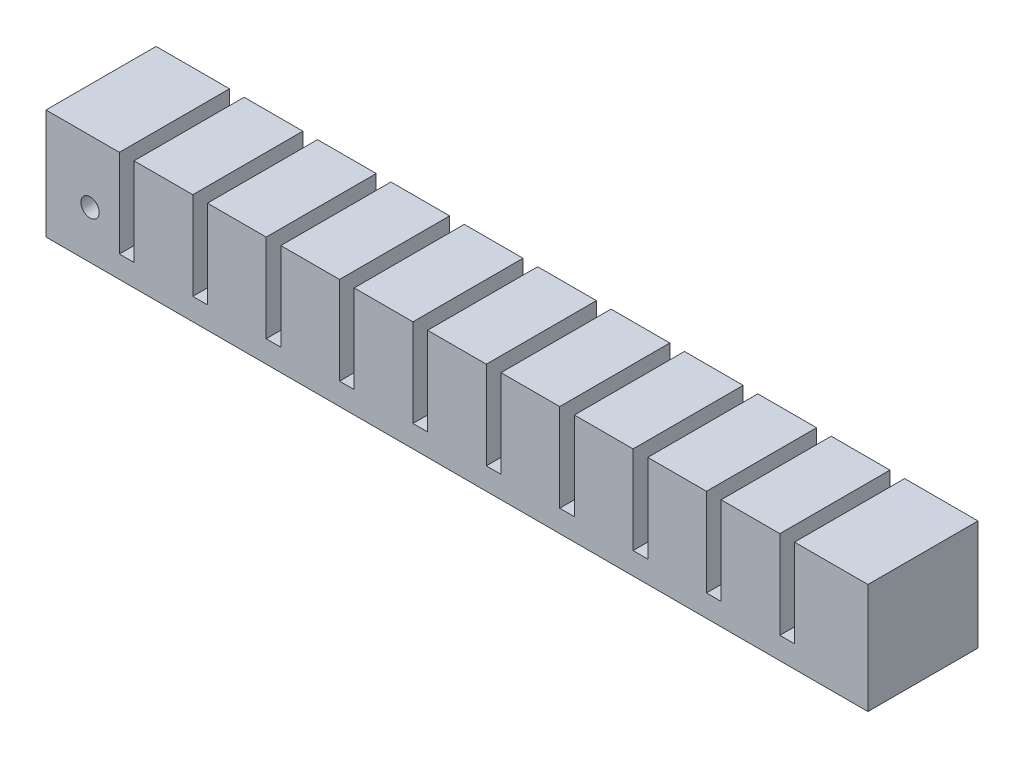
SolidWorks part; units mm, degrees
ref_plane "Front Plane" through (0, 0, 0) normal (0, 0, 1) x (1, 0, 0)
ref_plane "Top Plane" through (0, 0, 0) normal (0, 1, 0) x (1, 0, 0)
ref_plane "Right Plane" through (0, 0, 0) normal (1, 0, 0) x (0, 0, -1)
sketch "Sketch1" plane through (0, 0, 0) normal (0, 0, 1) x (1, 0, 0)
  line L1 (0, 0) -> (8, 0)
  line L2 (0, 0) -> (0, 15)
  line L3 (0, 15) -> (8, 15)
  line L4 (8, 0) -> (8, 15)
  dimension "D1" = 8
  dimension "D2" = 15
extrude "first chamber block" add sketch "Sketch1" along normal blind 15
sketch "Sketch2" plane through (0, 0, 0) normal (0, -1, 0) x (1, 0, 0)
  line L0 (8, 15) -> (8, 0) construction
  line L1 (1, 13) -> (7, 13)
  line L2 (1, 13) -> (1, 2)
  line L3 (1, 2) -> (7, 2)
  line L4 (7, 13) -> (7, 2)
  line L5 (0, 15) -> (0, 0) construction
  line L6 (0, 15) -> (8, 15) construction
  line L7 (0, 0) -> (8, 0) construction
  dimension "D1" = 1
  dimension "D2" = 1
  dimension "D3" = 2
  dimension "D4" = 2
extrude "first chamber cavity" cut sketch "Sketch2" against normal blind 13
sketch "Sketch3" plane through (8, 0, 0) normal (1, 0, 0) x (0, 0, -1)
  line L0 (-15, 0) -> (-15, 15) construction
  line L1 (0, 0) -> (-15, 0)
  line L2 (0, 0) -> (0, 3)
  line L3 (0, 3) -> (-15, 3)
  line L4 (-15, 0) -> (-15, 3)
  dimension "D1" = 3
extrude "chamber spacer" add sketch "Sketch3" along normal blind 2
pattern_linear "pattern chambers" count 11 spacing 10 along (1, 0, 0) of "chamber spacer", "first chamber cavity", "first chamber block"
combine bodies "combine into 1 solid body" operation type add bodies to combine 123 122 121 120 119 118 117 116 115 114 103
sketch "Sketch4" plane through (108, 0, 0) normal (1, 0, 0) x (0, 0, -1)
  line L1 (0, 15) -> (-15, 15)
  line L2 (0, 15) -> (0, 3)
  line L3 (0, 3) -> (-15, 3)
  line L4 (-15, 15) -> (-15, 3)
extrude "thicken end 1" add sketch "Sketch4" along normal up to surface (2 mm away) up to face at (110, 1.5, 7.5)
sketch "Sketch5" plane through (0, 0, 0) normal (-1, 0, 0) x (0, 0, 1)
  line L1 (15, 15) -> (0, 15)
  line L2 (15, 15) -> (15, 0)
  line L3 (15, 0) -> (0, 0)
  line L4 (0, 15) -> (0, 0)
extrude "thicken end 2" add sketch "Sketch5" along normal blind 2
ref_point "center of bottom face"
sketch "Sketch6" plane through (0, 0, 0) normal (0, -1, 0) x (1, 0, 0)
  line L0 (7, 2) -> (7, 13) construction
  line L1 (101, 6.5) -> (7, 6.5)
  line L2 (101, 6.5) -> (101, 8.5)
  line L3 (101, 8.5) -> (7, 8.5)
  line L4 (7, 6.5) -> (7, 8.5)
  line L5 (101, 6.5) -> (7, 8.5) construction
  line L6 (101, 8.5) -> (7, 6.5) construction
  point P0 (54, 7.5)
  dimension "D1" = 2
extrude "central air channel" cut sketch "Sketch6" against normal blind 2
sketch "Sketch7" plane through (0, 0, 0) normal (0, -1, 0) x (1, 0, 0)
  line L0 (0, 14) -> (108, 14)
  line L1 (1, 13) -> (107, 13)
  line L2 (1, 13) -> (1, 2)
  line L3 (1, 2) -> (107, 2)
  line L4 (107, 13) -> (107, 2)
  line L5 (108, 14) -> (108, 1)
  line L6 (0, 1) -> (108, 1)
  line L7 (0, 14) -> (0, 1)
  dimension "D1" = 1
extrude "bonding ridge" add sketch "Sketch7" along normal blind 2
sketch "Sketch9" plane through (0, 0, 0) normal (0, -1, 0) x (1, 0, 0)
  line L0 (11, 8.5) -> (11, 13) construction
  line L1 (11, 13) -> (7, 13) construction
  line L2 (7, 13) -> (7, 8.5) construction
  line L3 (7, 8.5) -> (11, 8.5) construction
  line L4 (7, 6.5) -> (7, 2) construction
  line L5 (7, 2) -> (11, 2) construction
  line L6 (11, 2) -> (11, 6.5) construction
  line L7 (11, 6.5) -> (7, 6.5) construction
  line L8 (11, 8.5) -> (11, 13) construction
  line L9 (11, 13) -> (7, 13) construction
  line L10 (7, 13) -> (7, 8.5) construction
  line L11 (7, 8.5) -> (11, 8.5) construction
  line L12 (7, 6.5) -> (7, 2) construction
  line L13 (7, 2) -> (11, 2) construction
  line L14 (11, 2) -> (11, 6.5) construction
  line L15 (11, 6.5) -> (7, 6.5) construction
  line L16 (10, 9.5) -> (10, 12)
  line L17 (10, 12) -> (8, 12)
  line L18 (8, 12) -> (8, 9.5)
  line L19 (8, 9.5) -> (10, 9.5)
  line L20 (8, 5.5) -> (8, 3)
  line L21 (8, 3) -> (10, 3)
  line L22 (10, 3) -> (10, 5.5)
  line L23 (10, 5.5) -> (8, 5.5)
  dimension "D1" = 1
extrude "bonding bumps" add sketch "Sketch9" along normal blind 2
pattern_linear "pattern bonding bumps" count 10 spacing 10 along (1, 0, 0) of "bonding bumps"
sketch "Skizze1" plane through (0, 0, 0) normal (0, -1, 0) x (1, 0, 0)
  line L4 (-2, 0) -> (110, 0)
  line L5 (110, 0) -> (110, 15)
  line L6 (110, 15) -> (-2, 15)
  line L7 (-2, 15) -> (-2, 0)
  line L8 (-2, 0) -> (110, 0)
  line L9 (110, 0) -> (110, 15)
  line L10 (110, 15) -> (-2, 15)
  line L11 (-2, 15) -> (-2, 0)
  dimension "D1" = 0
extrude "Schnitt-Linear austragen1" cut sketch "Skizze1" along normal through all
sketch "Skizze2" plane through (0, 3, 0) normal (0, 1, 0) x (1, 0, 0)
  line L0 (98, 0) -> (98, -15) construction
  line L1 (100, 0) -> (98, 0)
  line L2 (100, 0) -> (100, -1)
  line L3 (100, -1) -> (98, -1)
  line L4 (98, 0) -> (98, -1)
  line L5 (100, 0) -> (100, -15) construction
  line L6 (98, -15) -> (100, -15)
  line L7 (98, -15) -> (98, -14)
  line L8 (98, -14) -> (100, -14)
  line L9 (100, -15) -> (100, -14)
  dimension "D1" = 1
extrude "Aufsatz-Linear austragen1" [suppressed] add sketch "Skizze2" along normal offset from surface (9 mm away) 3
pattern_linear "Lineares Muster1" [suppressed] count 10 spacing 10 of bodies 151
sketch "Skizze3" plane through (0, 0, 2) normal (0, 0, 1) x (1, 0, 0)
  line L0 (104, 0) -> (104, 13) construction
  line L1 (107, 0) -> (101, 0) construction
  line L2 (101, 13) -> (107, 13) construction
  circle A0 centre (104, 6.8582) radius 1.25
  dimension "D1" = 2.5
extrude "Schnitt-Linear austragen2" [suppressed] cut sketch "Skizze3" along normal through all
sketch "Skizze4" plane through (0, 0, 2) normal (0, 0, 1) x (1, 0, 0)
  line L0 (4, 13) -> (4, 0) construction
  line L1 (1, 13) -> (7, 13) construction
  line L2 (7, 0) -> (1, 0) construction
  circle A0 centre (4, 6.5) radius 1.25
  dimension "D1" = 2.5
extrude "Schnitt-Linear austragen3" cut sketch "Skizze4" along normal through all
